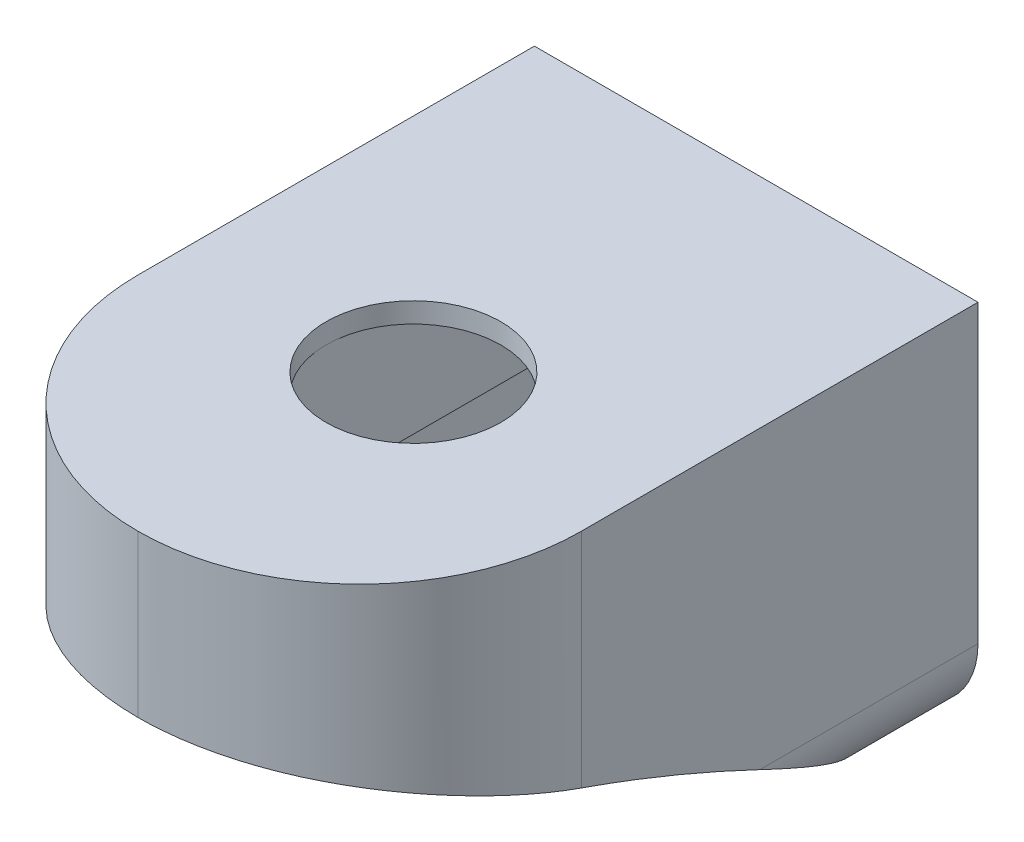
SolidWorks part; units mm, degrees
material "Acrylic (Medium-high impact)"
ref_plane "Front Plane" through (0, 0, 0) normal (0, 0, 1) x (1, 0, 0)
ref_plane "Top Plane" through (0, 0, 0) normal (0, 1, 0) x (1, 0, 0)
ref_plane "Right Plane" through (0, 0, 0) normal (1, 0, 0) x (0, 0, -1)
sketch "Sketch1" plane through (0, 0, 0) normal (0, 0, 1) x (1, 0, 0)
  line L1 (16.5, 14) -> (-16.5, 14)
  line L2 (16.5, 14) -> (16.5, -14)
  line L3 (16.5, -14) -> (-16.5, -14)
  line L4 (-16.5, 14) -> (-16.5, -14)
  line L5 (16.5, 14) -> (-16.5, -14) construction
  line L6 (16.5, -14) -> (-16.5, 14) construction
  point P0 (0, 0)
  dimension "D1" = 33
  dimension "D2" = 28
extrude "Boss-Extrude1" add sketch "Sketch1" along normal blind 46 contours L2 L1 L4 L3
sketch "Sketch2" plane through (16.5, 0, 0) normal (1, 0, 0) x (0, 0, -1)
  line L0 (-46, -14) -> (0, -14) construction
  line L1 (-46, 14) -> (-46, -14) construction
  line L2 (-46, 2) -> (-46, -14)
  line L3 (-46, -14) -> (-5, -14)
  line L4 (0, 14) -> (0, -14) construction
  line L5 (-46, 14) -> (0, 14) construction
  spline S0 degree 2 poles (-5, -14) (-24.4458, -2.4347) (-46, 2) knots 0 0 0 1 1 1
  dimension "D1" = 5
  dimension "D2" = 12
extrude "Cut-Extrude1" cut sketch "Sketch2" against normal through all
sketch "Sketch3" plane through (16.5, 0, 0) normal (1, 0, 0) x (0, 0, -1)
  line L0 (-5, -14) -> (-2.5, -14)
  line L1 (-5, -14) -> (0, -14) construction
  line L2 (-2.5, -14) -> (-2.5, 3.5)
  line L3 (-2.5, 3.5) -> (-40.5, 3.5)
  line L4 (-40.5, 3.5) -> (-40.5, 0.7437)
  parabola Q0 (-5, -14) -> (-46, 2) focus (-53.6889, -62.6693) apex (-35.3547, -0.663) construction
  parabola Q2 (-5, -14) -> (-46, 2) focus (-53.6889, -62.6693) apex (-35.3547, -0.663) construction
  parabola Q3 (-5, -14) -> (-40.5, 0.7437) focus (-53.6889, -62.6693) apex (-35.3547, -0.663)
  dimension "D1" = 17.5
  dimension "D2" = 38
extrude "Cut-Extrude2" cut sketch "Sketch3" against normal blind 27 from offset 3 offset against normal yes
fillet "Fillet1" radius 12.5 2 edges at (13.5, 2.1218, 40.5) (-13.5, 2.1218, 40.5)
fillet "Fillet2" radius 16.5 2 edges at (16.5, 8, 46) (-16.5, 8, 46)
fillet "Fillet3" radius 6 2 edges at (-16.5, -14, 2.5) (16.5, -14, 2.5)
sketch "Sketch4" plane through (0, 3.5, 0) normal (0, -1, 0) x (1, 0, 0)
  line L0 (0, 0) -> (0, 46) construction
  line L1 (-13.5, 2.5) -> (13.5, 2.5) construction
  line L2 (-6.5, 32) -> (6.5, 32)
  line L3 (-6.5, 32) -> (-6.5, 9)
  line L4 (-6.5, 9) -> (6.5, 9)
  line L5 (6.5, 32) -> (6.5, 9)
  line L6 (-6.5, 32) -> (6.5, 9) construction
  line L7 (-6.5, 9) -> (6.5, 32) construction
  point P4 (0, 20.5)
  dimension "D1" = 6.5
  dimension "D2" = 23
  dimension "D3" = 13
extrude "Cut-Extrude3" cut sketch "Sketch4" against normal blind 9
sketch "Sketch5" plane through (0, 12.5, 0) normal (0, -1, 0) x (1, 0, 0)
  line L0 (0, 32) -> (0, 9) construction
  line L1 (6.5, 32) -> (-6.5, 32) construction
  line L2 (-6.5, 9) -> (6.5, 9) construction
  circle A0 centre (0, 25.5) radius 6.5
  dimension "D1" = 13
extrude "Cut-Extrude4" cut sketch "Sketch5" against normal through all
sketch "Sketch6" plane through (0, 3.5, 0) normal (0, -1, 0) x (1, 0, 0)
  line L0 (-6.5, 20.5) -> (6.5, 20.5) construction
  line L1 (-6.5, 32) -> (-6.5, 9) construction
  line L2 (6.5, 9) -> (6.5, 32) construction
  line L3 (0, 34.3) -> (0, 6.7) construction
  circle A0 centre (0, 34.3) radius 1
  circle A1 centre (0, 6.7) radius 1
  point P10 (0, 20.5)
  dimension "D2" = 2
  dimension "D1" = 27.6
extrude "Cut-Extrude5" cut sketch "Sketch6" against normal blind 8
sketch "Sketch7" plane through (0, 0, 0) normal (0, 0, -1) x (-1, 0, 0)
  line L0 (0, 0) -> (-16.5, 0) construction
  line L1 (-16.5, 14) -> (-16.5, -8) construction
  line L2 (16.5, 14) -> (16.5, -8) construction
  circle A0 centre (0.5, 0) radius 1.3
  circle A1 centre (5, 0) radius 2.5
  circle A2 centre (9.5, 0) radius 1.3
  dimension "D1" = 2.6
  dimension "D2" = 5
  dimension "D3" = 11.5
  dimension "D4" = 9
  dimension "D5" = 4.5
extrude "Cut-Extrude6" cut sketch "Sketch7" against normal up to surface (2.5 mm away) up to face at (0, -7.9645, 2.5)
